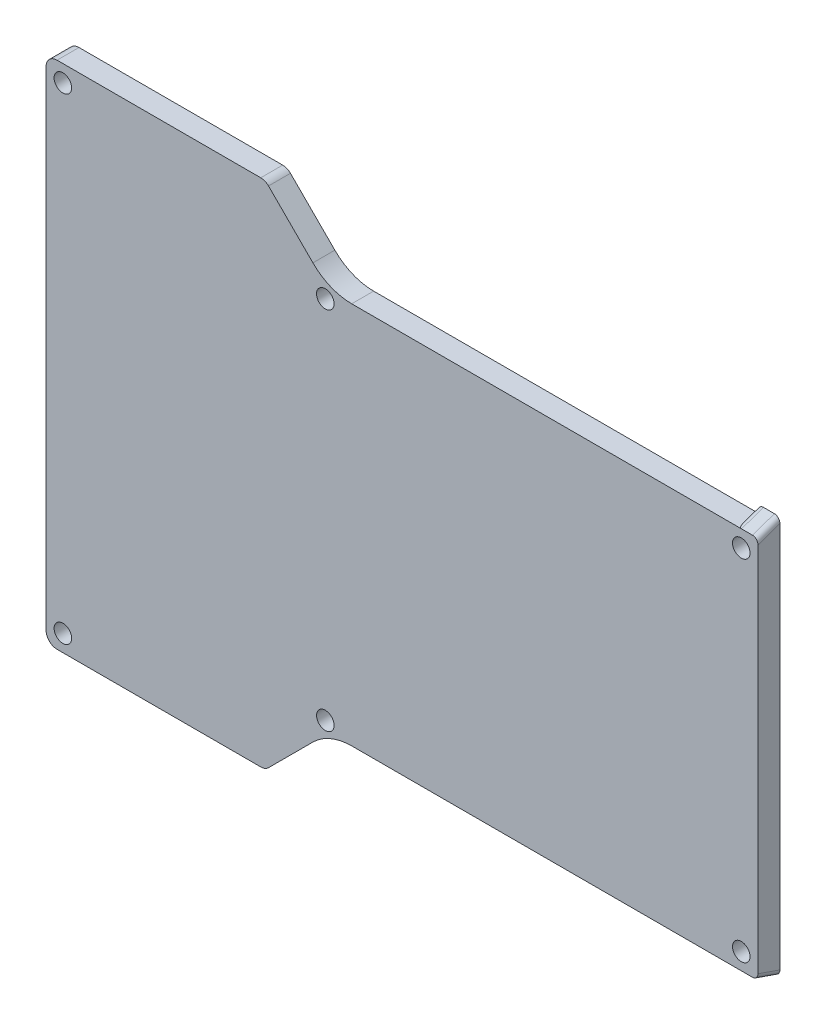
SolidWorks part; units mm, degrees
ref_plane "Front Plane" through (0, 0, 0) normal (0, 0, 1) x (1, 0, 0)
ref_plane "Top Plane" through (0, 0, 0) normal (0, 1, 0) x (1, 0, 0)
ref_plane "Right Plane" through (0, 0, 0) normal (1, 0, 0) x (0, 0, -1)
sketch "Sketch1" plane through (0, 0, 0) normal (0, 0, 1) x (1, 0, 0)
  line L12 (-16.3, -104.2696) -> (20.8284, -104.2696)
  line L13 (22.2426, -103.6838) -> (30.3379, -95.5885)
  line L14 (37.409, -92.6596) -> (107.455, -92.6596)
  line L15 (107.455, -92.6596) -> (107.455, -94.055)
  line L16 (111.455, -94.055) -> (107.455, -94.055)
  line L17 (111.455, -94.055) -> (111.455, -21.4798)
  line L18 (111.455, -21.4798) -> (107.455, -21.4798)
  line L19 (107.455, -21.4798) -> (107.455, -22.8746)
  line L20 (107.455, -22.8746) -> (37.404, -22.8746)
  line L21 (30.3329, -19.9457) -> (22.2426, -11.8554)
  line L22 (20.8284, -11.2696) -> (-16.3, -11.2696)
  line L23 (-18.3, -13.2696) -> (-18.3, -102.2696)
  circle A12 centre (32.5961, -91.0402) radius 1.6
  circle A13 centre (108.4121, -89.6167) radius 1.6
  circle A14 centre (108.4121, -25.9175) radius 1.6
  circle A15 centre (32.5911, -24.494) radius 1.6
  circle A16 centre (-15.2393, -14.3303) radius 1.6
  circle A17 centre (-15.2393, -101.2089) radius 1.6
  arc A18 (-18.3, -102.2696) -> (-16.3, -104.2696) centre (-16.3, -102.2696) ccw
  arc A19 (20.8284, -104.2696) -> (22.2426, -103.6838) centre (20.8284, -102.2696) ccw
  arc A20 (37.409, -92.6596) -> (30.3379, -95.5885) centre (37.409, -102.6596) ccw
  arc A21 (30.3329, -19.9457) -> (37.404, -22.8746) centre (37.404, -12.8746) ccw
  arc A22 (22.2426, -11.8554) -> (20.8284, -11.2696) centre (20.8284, -13.2696) ccw
  arc A23 (-16.3, -11.2696) -> (-18.3, -13.2696) centre (-16.3, -13.2696) ccw
extrude "Boss-Extrude1" add sketch "Sketch1" along normal blind 4
sketch "Sketch2" plane through (111.455, 0, 0) normal (1, 0, 0) x (0, 0, -1)
  line L2 (29.28, -11.2696) -> (0.5, -21.3054)
  line L3 (0.5, -94.2295) -> (29.28, -104.2696)
  line L4 (0.5, -94.2295) -> (-5.1544, -92.2569)
  line L5 (-5.1544, -92.2569) -> (-5.1544, -96.6775)
  line L6 (-5.1544, -96.6775) -> (0.5, -96.6775)
  line L7 (0.5, -96.6775) -> (0.5, -94.2295)
  line L8 (0.5, -21.3054) -> (-5.5036, -23.3989)
  line L9 (-5.5036, -23.3989) -> (-5.5036, -17.849)
  line L10 (-5.5036, -17.849) -> (0.5, -17.849)
  line L11 (0.5, -17.849) -> (0.5, -21.3054)
  line M2 (0, -21.4798) -> (-4, -21.4798)
  line M3 (-4, -21.4798) -> (-4, -94.055)
  line M4 (-4, -94.055) -> (0, -94.055)
extrude "Cut-Extrude2" cut sketch "Sketch2" against normal blind 4 contours L6 L7 L4 L5 M4 M3 | L11 L10 L9 L8 M3 M2 | L4 M4 M3 | L8 M2 M3 region at (111.455, -95.1352, 2.5863) region at (111.455, -19.9336, 2.7422) region at (111.455, -21.9447, 2.6667) region at (111.455, -93.5899, 2.6667)
fillet "Fillet1" radius 1 2 edges at (107.455, -93.3573, 2) (111.455, -93.3573, 2)
fillet "Fillet2" radius 1 2 edges at (111.455, -22.1772, 2) (107.455, -22.1772, 2)
